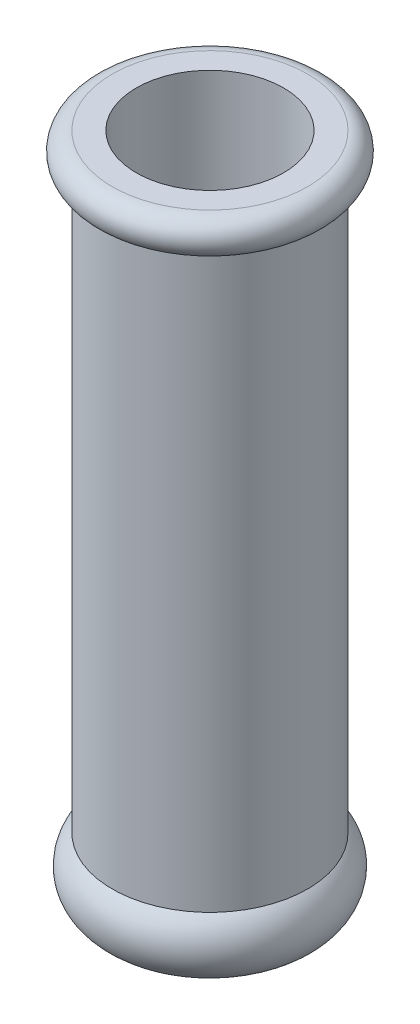
SolidWorks part; units mm, degrees
material "Rubber"
ref_plane "Front Plane" through (0, 0, 0) normal (0, 0, 1) x (1, 0, 0)
ref_plane "Top Plane" through (0, 0, 0) normal (0, 1, 0) x (1, 0, 0)
ref_plane "Right Plane" through (0, 0, 0) normal (1, 0, 0) x (0, 0, -1)
ref_axis "X-axis" through (-88.99, 0, 0) along (1, 0, 0)
ref_axis "Y-axis" through (0, 55, 0) along (0, -1, 0)
ref_axis "Z-axis" through (0, 0, -88.99) along (0, 0, 1)
sketch "Sketch1" plane through (0, 0, 0) normal (0, 0, 1) x (1, 0, 0)
  line L0 (-4.11, 37.6) -> (-4.11, 0)
  line L1 (0, 0) -> (0, 37.6) construction
  line L2 (-4.11, 37.6) -> (-5.45, 37.6)
  line L3 (-5.45, 35.6) -> (-5.45, 3.6562)
  arc A0 (-5.45, 37.6) -> (-5.45, 35.6) centre (-5.45, 36.6) ccw
  arc A1 (-5.45, 3.6562) -> (-4.11, 0) centre (-4.11, 2.0736) ccw
  dimension "D3" = 1
  dimension "D5" = 2.0736
  dimension "D1" = 8.22
  dimension "D2" = 10.9
  dimension "D4" = 37.6
  dimension "D6" = 31.9438
revolve "Revolve1" add sketch "Sketch1" angle 360 about L1
